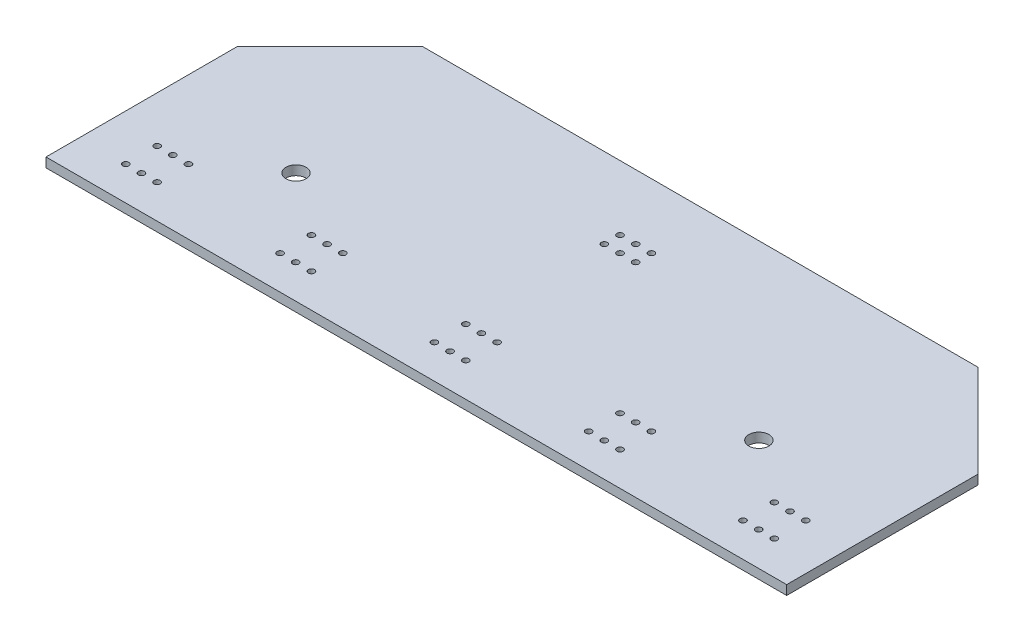
SolidWorks part; units mm, degrees
ref_plane "Front Plane" through (0, 0, 0) normal (0, 0, 1) x (1, 0, 0)
ref_plane "Top Plane" through (0, 0, 0) normal (0, 1, 0) x (1, 0, 0)
ref_plane "Right Plane" through (0, 0, 0) normal (1, 0, 0) x (0, 0, -1)
sketch "Sketch1" plane through (0, 0, 0) normal (0, 1, 0) x (1, 0, 0)
  line L0 (0, 0) -> (0, 13) construction
  line L1 (-60, -22) -> (60, -22)
  line L2 (-60, -22) -> (-60, 28)
  line L3 (-60, 28) -> (60, 28)
  line L4 (60, -22) -> (60, 28)
  line L5 (0, 0) -> (60, 28) construction
  line L6 (-60, 28) -> (0, 0) construction
  line L11 (0, 13) -> (0, 28) construction
  point P0 (0, 0)
  dimension "D1" = 120
  dimension "D2" = 28
  dimension "D6" = 22
extrude "Boss-Extrude1" add sketch "Sketch1" along normal blind 1.53
sketch "Sketch2" plane through (0, 1.53, 0) normal (0, 1, 0) x (1, 0, 0)
  line L0 (0, -10) -> (4.8827, -10) construction
  line L24 (-2.54, -7.46) -> (0, -7.46) construction
  line L25 (0, -7.46) -> (2.54, -7.46) construction
  line L26 (0, -7.46) -> (0, -12.54) construction
  line L27 (0, -12.54) -> (2.54, -12.54) construction
  line L28 (0, -12.54) -> (-2.54, -12.54) construction
  line L29 (0, -7.46) -> (0, 0) construction
  circle A25 centre (-2.54, -7.46) radius 0.5
  circle A26 centre (0, -7.46) radius 0.5
  circle A27 centre (2.54, -7.46) radius 0.5
  circle A28 centre (-2.54, -12.54) radius 0.5
  circle A29 centre (0, -12.54) radius 0.5
  circle A30 centre (2.54, -12.54) radius 0.5
  dimension "D1" = 10
  dimension "D2" = 1
  dimension "D8" = 5.08
  dimension "D9" = 2.54
extrude "PushButtonHoles" cut sketch "Sketch2" against normal through all
sketch "Sketch7" plane through (0, 1.53, 0) normal (0, 1, 0) x (1, 0, 0)
  line L0 (-37.5, 0) -> (0, 0) construction
  line L1 (0, 0) -> (37.5, 0) construction
  circle A0 centre (-37.5, 0) radius 1.625
  circle A1 centre (37.5, 0) radius 1.625
  dimension "D1" = 3.25
  dimension "D2" = 37.5
extrude "Mount Holes" cut sketch "Sketch7" against normal through all
sketch "Sketch5" plane through (0, 1.53, 0) normal (0, 1, 0) x (1, 0, 0)
  line L0 (-2.54, 17.54) -> (0, 17.54) construction
  line L1 (0, 17.54) -> (2.54, 17.54) construction
  line L2 (0, 17.54) -> (0, 15) construction
  line L3 (0, 15) -> (2.54, 15) construction
  line L4 (0, 15) -> (-2.54, 15) construction
  line L5 (0, 0) -> (0, 15) construction
  circle A0 centre (-2.54, 17.54) radius 0.5
  circle A1 centre (0, 17.54) radius 0.5
  circle A2 centre (2.54, 17.54) radius 0.5
  circle A3 centre (-2.54, 15) radius 0.5
  circle A4 centre (0, 15) radius 0.5
  circle A5 centre (2.54, 15) radius 0.5
  dimension "D1" = 2.54
  dimension "D2" = 2.54
  dimension "D3" = 15
extrude "RJ12Holes" cut sketch "Sketch5" against normal through all
sketch "Sketch6" plane through (0, 1.53, 0) normal (0, 1, 0) x (1, 0, 0)
  line L0 (-45, 28) -> (-60, 13)
  line L1 (60, 28) -> (-60, 28) construction
  line L2 (-60, 28) -> (-60, -22) construction
  line L3 (-60, 13) -> (-60, -18)
  line L5 (-60, -22) -> (60, -22) construction
  line L6 (-52, -22) -> (-28, -22)
  line L8 (-60, -18) -> (60, -18)
  line L12 (60, -22) -> (60, 28) construction
  line L13 (60, -18) -> (60, 13)
  line L14 (60, 13) -> (45, 28)
  line L15 (45, 28) -> (-45, 28)
  line L16 (0, 0) -> (0, -18) construction
  line L17 (0, 0) -> (0, 28) construction
  line L18 (-70.5255, 34.7658) -> (-70.5255, -34.7658)
  line L23 (-70.5255, -34.7658) -> (70.5255, 34.7658) construction
  line L24 (-70.5255, 34.7658) -> (70.5255, -34.7658) construction
  line L25 (-70.5255, -34.7658) -> (70.5255, -34.7658)
  line L26 (70.5255, -34.7658) -> (70.5255, 34.7658)
  line L27 (70.5255, 34.7658) -> (-70.5255, 34.7658)
  line M37 (60, -22) -> (60, 28)
  line M38 (60, 28) -> (-60, 28)
  line M39 (-60, 28) -> (-60, -22)
  line M40 (-60, -22) -> (60, -22)
  dimension "D1" = 45
  dimension "D3" = 90
  dimension "D5" = 18
extrude "Cut-Extrude4" cut sketch "Sketch6" against normal through all contours L26 L27 L18 L25 M37 M40 M39 M38 | L8 M39 M40 M37 | L0 M38 M39 | L14 M37 M38
pattern_linear "LPattern1" count 3 spacing 25 along (1, 0, 0) count 3 spacing 25 along (-1, 0, 0) of "PushButtonHoles" pattern seed only yes
